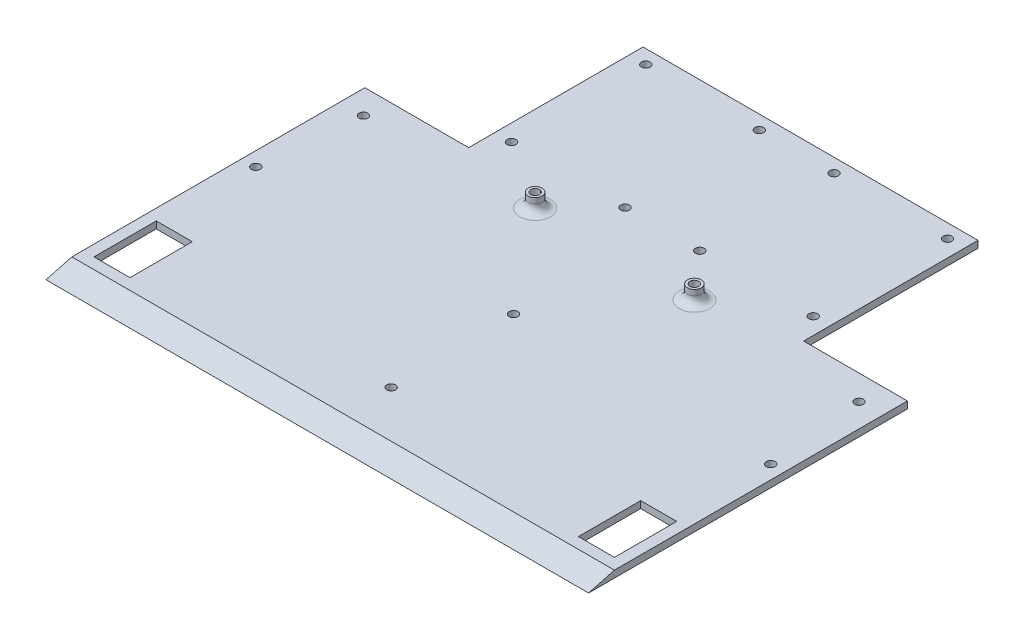
SolidWorks part; units mm, degrees
ref_plane "Alzado" through (0, 0, 0) normal (0, 0, 1) x (1, 0, 0)
ref_plane "Planta" through (0, 0, 0) normal (0, 1, 0) x (1, 0, 0)
ref_plane "Vista lateral" through (0, 0, 0) normal (1, 0, 0) x (0, 0, -1)
sketch "Croquis1" plane through (0, 0, 0) normal (1, 0, 0) x (0, 0, -1)
  line L0 (0, 0) -> (178.17, 0)
  line L1 (178.17, 0) -> (178.17, 2.5)
  line L2 (178.17, 2.5) -> (9.3301, 2.5)
  line L3 (0, 0) -> (9.3301, 2.5)
  dimension "D1" = 178.17
  dimension "D2" = 2.5
  dimension "D3" = 165
extrude "Saliente-Extruir1" add sketch "Croquis1" along normal blind 196
sketch "Croquis2" plane through (0, 0, 0) normal (0, -1, 0) x (-1, 0, 0)
  line L1 (-37.5, 115.1801) -> (0, 115.1801)
  line L2 (-37.5, 115.1801) -> (-37.5, 178.17)
  line L3 (-37.5, 178.17) -> (0, 178.17)
  line L4 (0, 115.1801) -> (0, 178.17)
  line L5 (-37.5, 115.1801) -> (0, 178.17) construction
  line L6 (-37.5, 178.17) -> (0, 115.1801) construction
  line L7 (-158.5, 115.1801) -> (-196, 115.1801)
  line L8 (-158.5, 115.1801) -> (-158.5, 178.17)
  line L9 (-158.5, 178.17) -> (-196, 178.17)
  line L10 (-196, 115.1801) -> (-196, 178.17)
  line L11 (-158.5, 115.1801) -> (-196, 178.17) construction
  line L12 (-158.5, 178.17) -> (-196, 115.1801) construction
  point P4 (-18.75, 146.6751)
  point P11 (-177.25, 146.6751)
extrude "Cortar-Extruir1" cut sketch "Croquis2" against normal up to next
sketch "Croquis4" plane through (0, 2.5, 0) normal (0, 1, 0) x (1, 0, 0)
  line L7 (4, 13.3301) -> (17, 13.3301)
  line L8 (4, 13.3301) -> (4, 35.8301)
  line L9 (4, 35.8301) -> (17, 35.8301)
  line L10 (17, 13.3301) -> (17, 35.8301)
  line L11 (4, 13.3301) -> (17, 35.8301) construction
  line L12 (4, 35.8301) -> (17, 13.3301) construction
  point P9 (10.5, 24.5801)
  dimension "D3" = 22.5
  dimension "D4" = 13
extrude "Cortar-Extruir2" cut sketch "Croquis4" against normal up to next
ref_plane "Plano1" through (98, 0, 0) normal (1, 0, 0) x (0, 0, -1)
mirror "Simetría1" about plane through (98, 0, 0) normal (1, 0, 0) of "Cortar-Extruir2"
sketch "Sketch1" plane through (0, 2.5, 0) normal (0, 1, 0) x (1, 0, 0)
  circle A0 centre (187.5, 106.1801) radius 1.585
  circle A1 centre (8.5, 106.1801) radius 1.585
extrude "Cut-Extrude1" cut sketch "Sketch1" against normal up to next
sketch "Sketch2" plane through (0, 2.5, 0) normal (0, 1, 0) x (1, 0, 0)
  circle A0 centre (98.5, 26.1801) radius 1.585
extrude "Cut-Extrude2" cut sketch "Sketch2" against normal up to next
sketch "Sketch3" plane through (0, 2.5, 0) normal (0, 1, 0) x (1, 0, 0)
  circle A0 centre (111.5, 124.67) radius 1.585
  circle A1 centre (152.5, 124.67) radius 1.585
  circle A2 centre (152.5, 173.17) radius 1.585
  circle A3 centre (111.5, 173.17) radius 1.585
  circle A4 centre (84.5, 173.17) radius 1.585
  circle A5 centre (43.5, 173.17) radius 1.585
  circle A6 centre (43.5, 124.67) radius 1.585
  circle A7 centre (84.5, 124.67) radius 1.585
extrude "Cut-Extrude3" cut sketch "Sketch3" against normal up to next
sketch "Sketch4" plane through (0, 2.5, 0) normal (0, 1, 0) x (1, 0, 0)
  circle A0 centre (125.8764, 108.3369) radius 1.6
  circle A1 centre (68.4153, 108.2804) radius 1.6
  circle A2 centre (68.4153, 108.2804) radius 2.5
  circle A3 centre (125.8764, 108.3369) radius 2.5
  dimension "D1" = 5
  dimension "D2" = 5
extrude "Boss-Extrude1" add sketch "Sketch4" along normal blind 5
sketch "Sketch7" plane through (0, 2.5, 0) normal (0, 1, 0) x (1, 0, 0)
  circle A0 centre (5.0671, 70.7278) radius 1.585
  circle A1 centre (97.6819, 71.2085) radius 1.585
  circle A2 centre (191.0671, 70.7278) radius 1.585
extrude "Cut-Extrude5" cut sketch "Sketch7" against normal blind 10
sketch "Sketch8" plane through (0, 2.5, 0) normal (0, 1, 0) x (1, 0, 0)
  circle A0 centre (68.4153, 108.2804) radius 1.6
  circle A1 centre (125.8764, 108.3369) radius 1.6
extrude "Cut-Extrude6" cut sketch "Sketch8" against normal through all
fillet "Fillet1" radius 3 2 edges at (68.4153, 2.5, -110.7804) (125.8764, 2.5, -110.8369)
